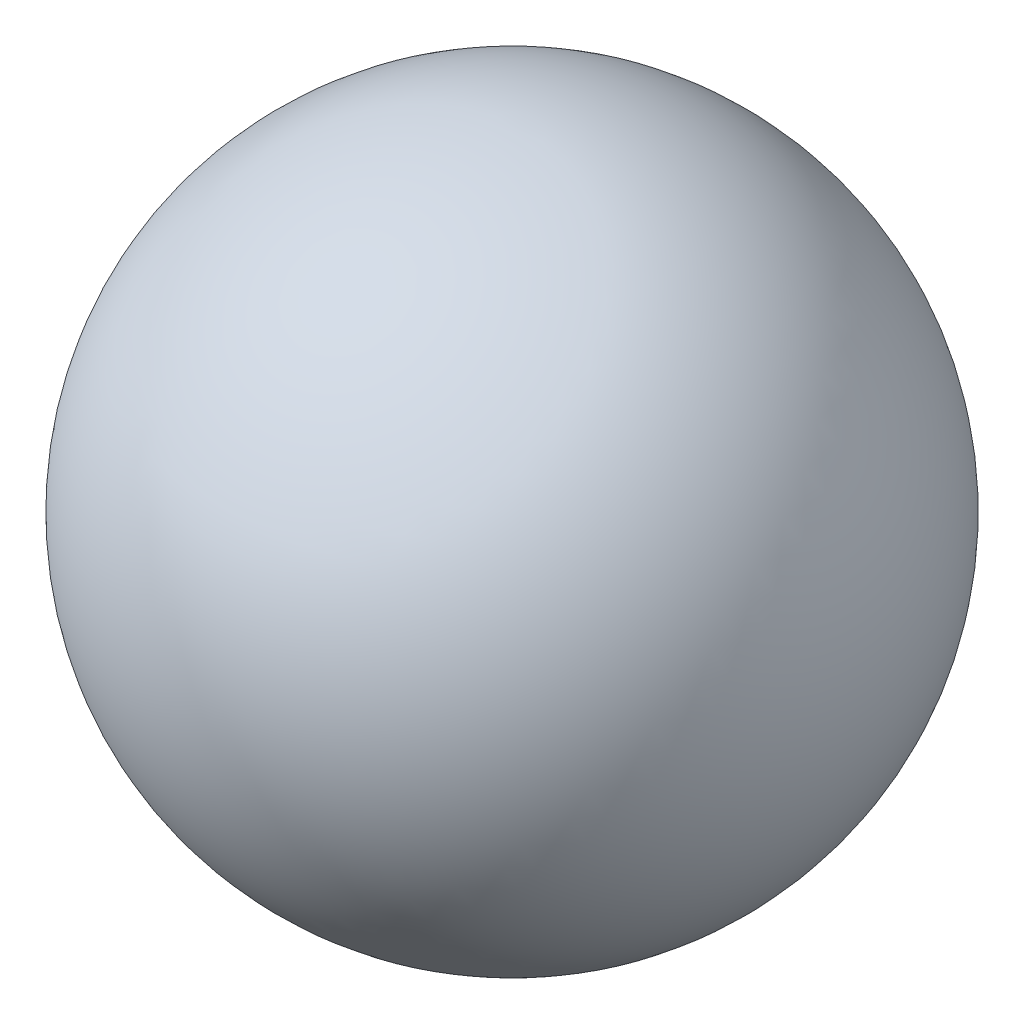
SolidWorks part; units mm, degrees
material "PVC 0.007 塑化"
ref_plane "前基準面" through (0, 0, 0) normal (0, 0, 1) x (1, 0, 0)
ref_plane "上基準面" through (0, 0, 0) normal (0, 1, 0) x (1, 0, 0)
ref_plane "右基準面" through (0, 0, 0) normal (1, 0, 0) x (0, 0, -1)
sketch "草圖1" plane through (0, 0, 0) normal (0, 0, 1) x (1, 0, 0)
  line L0 (0, 35) -> (0, -35)
  arc A0 (0, 35) -> (0, -35) centre (0, 0) cw
  point P4 (0, 0)
  point P6 (0, 0)
  dimension "D1" = 35
revolve "旋轉1" add sketch "草圖1" angle 360 about L0
